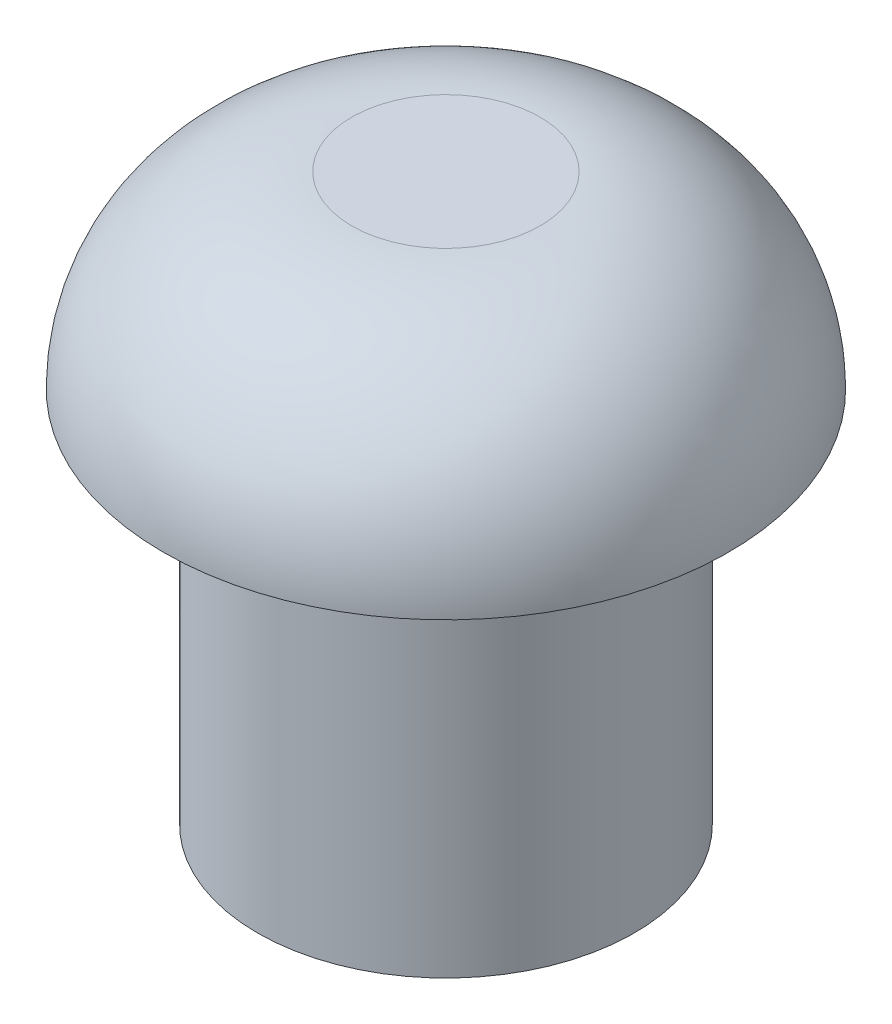
SolidWorks part; units mm, degrees
ref_plane "Front Plane" through (0, 0, 0) normal (0, 0, 1) x (1, 0, 0)
ref_plane "Top Plane" through (0, 0, 0) normal (0, 1, 0) x (1, 0, 0)
ref_plane "Right Plane" through (0, 0, 0) normal (1, 0, 0) x (0, 0, -1)
sketch "Sketch1" plane through (0, 0, 0) normal (0, 1, 0) x (1, 0, 0)
  circle A0 centre (0, 0) radius 5
  dimension "D1" = 10
extrude "Boss-Extrude1" add sketch "Sketch1" along normal blind 10
sketch "Sketch2" plane through (0, 10, 0) normal (0, 1, 0) x (1, 0, 0)
  circle A0 centre (0, 0) radius 7.5
  dimension "D1" = 15
extrude "Boss-Extrude2" add sketch "Sketch2" along normal blind 5
fillet "Fillet2" radius 5 1 edges at (0, 15, 7.5)
